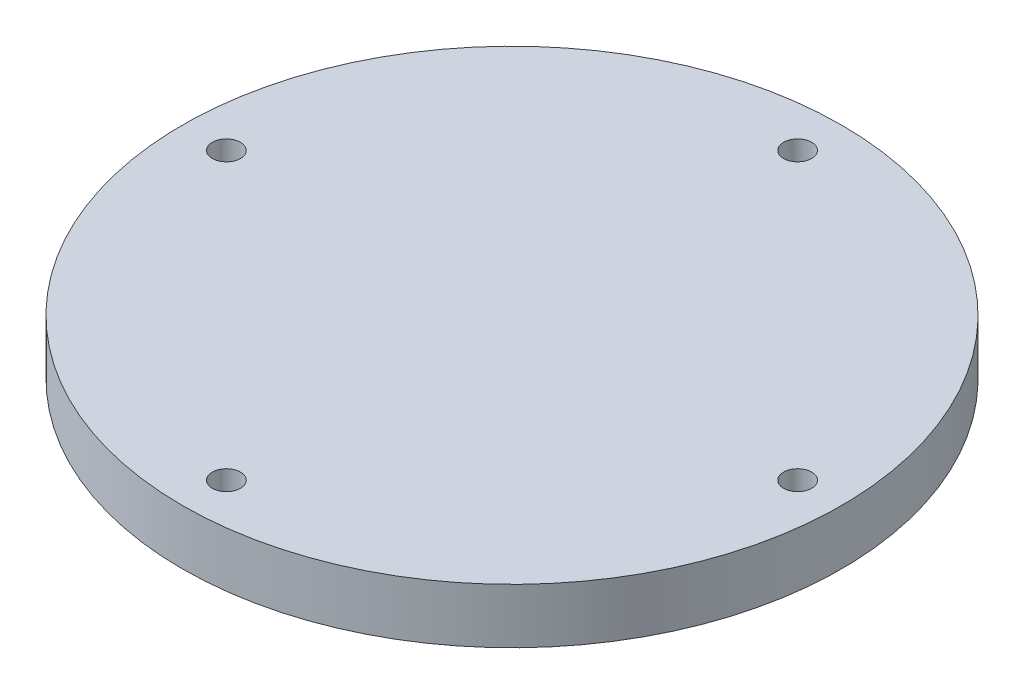
SolidWorks part; units mm, degrees
material "Acrylic (Medium-high impact)"
ref_plane "Front Plane" through (0, 0, 0) normal (0, 0, 1) x (1, 0, 0)
ref_plane "Top Plane" through (0, 0, 0) normal (0, 1, 0) x (1, 0, 0)
ref_plane "Right Plane" through (0, 0, 0) normal (1, 0, 0) x (0, 0, -1)
sketch "Sketch1" plane through (0, 0, 0) normal (0, 1, 0) x (1, 0, 0)
  circle A0 centre (0, 0) radius 38.1
  circle A1 centre (0, 33.02) radius 1.6256
  circle A2 centre (33.02, 0) radius 1.6256
  circle A3 centre (0, -33.02) radius 1.6256
  circle A4 centre (-33.02, 0) radius 1.6256
  point P14 (0, 0)
  dimension "D1" = 76.2
  dimension "D3" = 3.2512
  dimension "D4" = 33.02
  dimension "D2" = 4
extrude "Boss-Extrude1" add sketch "Sketch1" along normal blind 6.35
